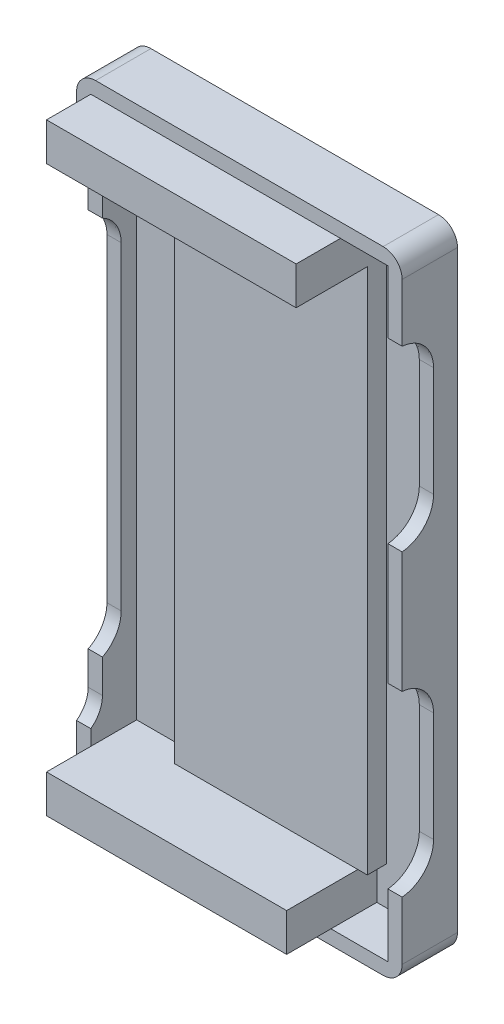
SolidWorks part; units mm, degrees
ref_plane "Front Plane" through (0, 0, 0) normal (0, 0, 1) x (1, 0, 0)
ref_plane "Top Plane" through (0, 0, 0) normal (0, 1, 0) x (1, 0, 0)
ref_plane "Right Plane" through (0, 0, 0) normal (1, 0, 0) x (0, 0, -1)
sketch "Sketch1" plane through (0, 0, 0) normal (0, 0, 1) x (1, 0, 0)
  line L0 (-32.3, 64.5) -> (2, 64.5)
  line L1 (-30.3, 62.5) -> (0, 62.5) construction
  line L2 (-30.3, 62.5) -> (-30.3, 0) construction
  line L3 (-30.3, 0) -> (0, 0) construction
  line L4 (0, 62.5) -> (0, 0) construction
  line L5 (2, 64.5) -> (2, -2)
  line L6 (-32.3, -2) -> (2, -2)
  line L7 (-32.3, 64.5) -> (-32.3, -2)
  dimension "D1" = 2
extrude "Boss-Extrude3" add sketch "Sketch1" along normal offset from surface 1.5 and the other way offset from surface (16.5814 mm away) 1.5
sketch "Sketch3" plane through (-32.3, 0, 0) normal (-1, 0, 0) x (0, 0, 1)
  line L0 (-13.4464, 47.86) -> (-13.4464, 14.26) construction
  line L1 (-9.7847, 11.1874) -> (-6.7947, 11.7146) construction
  line L2 (-4.2164, 14.7872) -> (-4.2164, 47.3328) construction
  line L3 (-6.7947, 50.4054) -> (-9.7847, 50.9326) construction
  line L5 (-13.9464, 47.86) -> (-13.9464, 14.26)
  line L6 (-9.6978, 10.695) -> (-6.7078, 11.2222)
  line L12 (-13.4464, 47.86) -> (-13.4464, 14.26) construction
  line L13 (-9.7847, 11.1874) -> (-6.7947, 11.7146) construction
  line L14 (-4.2164, 14.7872) -> (-4.2164, 47.3328) construction
  line L15 (-6.7947, 50.4054) -> (-9.7847, 50.9326) construction
  line L16 (-3.7164, 14.7872) -> (-3.7164, 47.3328)
  line L17 (-6.7078, 50.8978) -> (-9.6978, 51.425)
  spline S0 degree 3 poles (-13.4464, 14.26) (-13.4464, 12.1686) (-11.8443, 10.8242) (-9.7847, 11.1874) knots 0 0 0 0 1 1 1 1 weights 1 0.761858 0.761858 1 construction
  spline S1 degree 3 poles (-6.7947, 11.7146) (-5.2347, 11.9897) (-4.2164, 13.2032) (-4.2164, 14.7872) knots 0 0 0 0 1 1 1 1 weights 1 0.84403 0.84403 1 construction
  spline S2 degree 3 poles (-4.2164, 47.3328) (-4.2164, 48.9169) (-5.2347, 50.1303) (-6.7947, 50.4054) knots 0 0 0 0 1 1 1 1 weights 1 0.84403 0.84403 1 construction
  spline S3 degree 3 poles (-9.7847, 50.9326) (-11.8443, 51.2958) (-13.4464, 49.9514) (-13.4464, 47.86) knots 0 0 0 0 1 1 1 1 weights 1 0.761858 0.761858 1 construction
  spline S4 degree 3 poles (-13.4464, 14.26) (-13.4464, 12.1686) (-11.8443, 10.8242) (-9.7847, 11.1874) knots 0 0 0 0 1 1 1 1 weights 1 0.761858 0.761858 1 construction
  spline S5 degree 3 poles (-6.7947, 11.7146) (-5.2347, 11.9897) (-4.2164, 13.2032) (-4.2164, 14.7872) knots 0 0 0 0 1 1 1 1 weights 1 0.84403 0.84403 1 construction
  spline S6 degree 3 poles (-4.2164, 47.3328) (-4.2164, 48.9169) (-5.2347, 50.1303) (-6.7947, 50.4054) knots 0 0 0 0 1 1 1 1 weights 1 0.84403 0.84403 1 construction
  spline S7 degree 3 poles (-9.7847, 50.9326) (-11.8443, 51.2958) (-13.4464, 49.9514) (-13.4464, 47.86) knots 0 0 0 0 1 1 1 1 weights 1 0.761858 0.761858 1 construction
  spline S8 degree 1 poles (-13.9464, 14.26) (-9.6978, 10.695) knots 0 0 1 1 construction
  spline S9 degree 1 poles (-6.7078, 11.2222) (-3.7164, 14.7872) knots 0 0 1 1 construction
  spline S10 degree 1 poles (-3.7164, 47.3328) (-6.7078, 50.8978) knots 0 0 1 1 construction
  spline S11 degree 1 poles (-9.6978, 51.425) (-13.9464, 47.86) knots 0 0 1 1 construction
  spline S12 degree 3 poles (-13.9464, 14.26) (-13.9464, 14.0193) (-13.9017, 13.5499) (-13.5942, 12.5442) (-12.7412, 11.3822) (-11.4487, 10.7439) (-10.4049, 10.6158) (-9.9349, 10.6532) (-9.6978, 10.695) knots 0 0 0 0 0.125 0.25 0.5 0.75 0.875 1 1 1 1
  spline S13 degree 3 poles (-6.7078, 11.2222) (-6.308, 11.2927) (-5.5445, 11.5574) (-4.4978, 12.4053) (-3.8445, 13.5834) (-3.7164, 14.3812) (-3.7164, 14.7872) knots 0 0 0 0 0.25 0.5 0.75 1 1 1 1
  spline S14 degree 3 poles (-3.7164, 47.3328) (-3.7164, 47.7388) (-3.8445, 48.5366) (-4.4978, 49.7147) (-5.5445, 50.5626) (-6.308, 50.8273) (-6.7078, 50.8978) knots 0 0 0 0 0.25 0.5 0.75 1 1 1 1
  spline S15 degree 3 poles (-9.6978, 51.425) (-9.9349, 51.4668) (-10.4049, 51.5042) (-11.4487, 51.3761) (-12.7412, 50.7379) (-13.5942, 49.5758) (-13.9017, 48.5701) (-13.9464, 48.1007) (-13.9464, 47.86) knots 0 0 0 0 0.125 0.25 0.5 0.75 0.875 1 1 1 1
  dimension "D1" = 0.5
extrude "Cut-Extrude1" cut sketch "Sketch3" against normal blind 5
sketch "Sketch4" plane through (2, 0, 0) normal (1, 0, 0) x (0, 0, -1)
  line L0 (6.9047, 38.7046) -> (9.8947, 38.1774) construction
  line L1 (4.3264, 52.2728) -> (4.3264, 41.7772) construction
  line L2 (13.5564, 41.25) -> (13.5564, 52.8) construction
  line L3 (9.8947, 55.8726) -> (6.9047, 55.3454) construction
  line L4 (6.9047, 38.7046) -> (9.8947, 38.1774) construction
  line L5 (4.3264, 52.2728) -> (4.3264, 41.7772) construction
  line L6 (13.5564, 41.25) -> (13.5564, 52.8) construction
  line L7 (9.8947, 55.8726) -> (6.9047, 55.3454) construction
  line L8 (4.3264, 20.7728) -> (4.3264, 10.2772) construction
  line L9 (6.9047, 7.2046) -> (9.8947, 6.6774) construction
  line L10 (13.5564, 9.75) -> (13.5564, 21.3) construction
  line L11 (9.8947, 24.3726) -> (6.9047, 23.8454) construction
  line L12 (4.3264, 20.7728) -> (4.3264, 10.2772) construction
  line L13 (6.9047, 7.2046) -> (9.8947, 6.6774) construction
  line L14 (13.5564, 9.75) -> (13.5564, 21.3) construction
  line L15 (9.8947, 24.3726) -> (6.9047, 23.8454) construction
  line L16 (6.8178, 38.2122) -> (9.8078, 37.685)
  line L17 (14.0564, 41.25) -> (14.0564, 52.8)
  line L18 (9.8078, 56.365) -> (6.8178, 55.8378)
  line L19 (3.8264, 52.2728) -> (3.8264, 41.7772)
  line L20 (3.8264, 20.7728) -> (3.8264, 10.2772)
  line L21 (6.8178, 6.7122) -> (9.8078, 6.185)
  line L22 (14.0564, 9.75) -> (14.0564, 21.3)
  line L23 (9.8078, 24.865) -> (6.8178, 24.3378)
  spline S0 degree 3 poles (4.3264, 41.7772) (4.3264, 40.1932) (5.3447, 38.9797) (6.9047, 38.7046) knots 0 0 0 0 1 1 1 1 weights 1 0.84403 0.84403 1 construction
  spline S1 degree 3 poles (9.8947, 38.1774) (11.9543, 37.8142) (13.5564, 39.1586) (13.5564, 41.25) knots 0 0 0 0 1 1 1 1 weights 1 0.761858 0.761858 1 construction
  spline S2 degree 3 poles (6.9047, 55.3454) (5.3447, 55.0703) (4.3264, 53.8568) (4.3264, 52.2728) knots 0 0 0 0 1 1 1 1 weights 1 0.84403 0.84403 1 construction
  spline S3 degree 3 poles (13.5564, 52.8) (13.5564, 54.8914) (11.9543, 56.2358) (9.8947, 55.8726) knots 0 0 0 0 1 1 1 1 weights 1 0.761858 0.761858 1 construction
  spline S4 degree 3 poles (4.3264, 41.7772) (4.3264, 40.1932) (5.3447, 38.9797) (6.9047, 38.7046) knots 0 0 0 0 1 1 1 1 weights 1 0.84403 0.84403 1 construction
  spline S5 degree 3 poles (9.8947, 38.1774) (11.9543, 37.8142) (13.5564, 39.1586) (13.5564, 41.25) knots 0 0 0 0 1 1 1 1 weights 1 0.761858 0.761858 1 construction
  spline S6 degree 3 poles (6.9047, 55.3454) (5.3447, 55.0703) (4.3264, 53.8568) (4.3264, 52.2728) knots 0 0 0 0 1 1 1 1 weights 1 0.84403 0.84403 1 construction
  spline S7 degree 3 poles (13.5564, 52.8) (13.5564, 54.8914) (11.9543, 56.2358) (9.8947, 55.8726) knots 0 0 0 0 1 1 1 1 weights 1 0.761858 0.761858 1 construction
  spline S8 degree 3 poles (4.3264, 10.2772) (4.3264, 8.6932) (5.3447, 7.4797) (6.9047, 7.2046) knots 0 0 0 0 1 1 1 1 weights 1 0.84403 0.84403 1 construction
  spline S9 degree 3 poles (9.8947, 6.6774) (11.9543, 6.3142) (13.5564, 7.6586) (13.5564, 9.75) knots 0 0 0 0 1 1 1 1 weights 1 0.761858 0.761858 1 construction
  spline S10 degree 3 poles (6.9047, 23.8454) (5.3447, 23.5703) (4.3264, 22.3568) (4.3264, 20.7728) knots 0 0 0 0 1 1 1 1 weights 1 0.84403 0.84403 1 construction
  spline S11 degree 3 poles (13.5564, 21.3) (13.5564, 23.3914) (11.9543, 24.7358) (9.8947, 24.3726) knots 0 0 0 0 1 1 1 1 weights 1 0.761858 0.761858 1 construction
  spline S12 degree 3 poles (4.3264, 10.2772) (4.3264, 8.6932) (5.3447, 7.4797) (6.9047, 7.2046) knots 0 0 0 0 1 1 1 1 weights 1 0.84403 0.84403 1 construction
  spline S13 degree 3 poles (9.8947, 6.6774) (11.9543, 6.3142) (13.5564, 7.6586) (13.5564, 9.75) knots 0 0 0 0 1 1 1 1 weights 1 0.761858 0.761858 1 construction
  spline S14 degree 3 poles (6.9047, 23.8454) (5.3447, 23.5703) (4.3264, 22.3568) (4.3264, 20.7728) knots 0 0 0 0 1 1 1 1 weights 1 0.84403 0.84403 1 construction
  spline S15 degree 3 poles (13.5564, 21.3) (13.5564, 23.3914) (11.9543, 24.7358) (9.8947, 24.3726) knots 0 0 0 0 1 1 1 1 weights 1 0.761858 0.761858 1 construction
  spline S16 degree 1 poles (9.8078, 37.685) (14.0564, 41.25) knots 0 0 1 1 construction
  spline S17 degree 1 poles (14.0564, 52.8) (9.8078, 56.365) knots 0 0 1 1 construction
  spline S18 degree 1 poles (6.8178, 55.8378) (3.8264, 52.2728) knots 0 0 1 1 construction
  spline S19 degree 1 poles (3.8264, 41.7772) (6.8178, 38.2122) knots 0 0 1 1 construction
  spline S20 degree 3 poles (9.8078, 37.685) (10.0449, 37.6432) (10.5149, 37.6058) (11.5587, 37.7339) (12.8512, 38.3721) (13.7042, 39.5342) (14.0117, 40.5399) (14.0564, 41.0093) (14.0564, 41.25) knots 0 0 0 0 0.125 0.25 0.5 0.75 0.875 1 1 1 1
  spline S21 degree 3 poles (14.0564, 52.8) (14.0564, 53.0407) (14.0117, 53.5101) (13.7042, 54.5158) (12.8512, 55.6778) (11.5587, 56.3161) (10.5149, 56.4442) (10.0449, 56.4068) (9.8078, 56.365) knots 0 0 0 0 0.125 0.25 0.5 0.75 0.875 1 1 1 1
  spline S22 degree 3 poles (6.8178, 55.8378) (6.418, 55.7673) (5.6545, 55.5026) (4.6078, 54.6547) (3.9545, 53.4766) (3.8264, 52.6788) (3.8264, 52.2728) knots 0 0 0 0 0.25 0.5 0.75 1 1 1 1
  spline S23 degree 3 poles (3.8264, 41.7772) (3.8264, 41.3712) (3.9545, 40.5734) (4.6078, 39.3953) (5.6545, 38.5474) (6.418, 38.2827) (6.8178, 38.2122) knots 0 0 0 0 0.25 0.5 0.75 1 1 1 1
  spline S24 degree 1 poles (3.8264, 10.2772) (6.8178, 6.7122) knots 0 0 1 1 construction
  spline S25 degree 1 poles (9.8078, 6.185) (14.0564, 9.75) knots 0 0 1 1 construction
  spline S26 degree 1 poles (14.0564, 21.3) (9.8078, 24.865) knots 0 0 1 1 construction
  spline S27 degree 1 poles (6.8178, 24.3378) (3.8264, 20.7728) knots 0 0 1 1 construction
  spline S28 degree 3 poles (3.8264, 10.2772) (3.8264, 9.8712) (3.9545, 9.0734) (4.6078, 7.8953) (5.6545, 7.0474) (6.418, 6.7827) (6.8178, 6.7122) knots 0 0 0 0 0.25 0.5 0.75 1 1 1 1
  spline S29 degree 3 poles (9.8078, 6.185) (10.0449, 6.1432) (10.5149, 6.1058) (11.5587, 6.2339) (12.8512, 6.8722) (13.7042, 8.0342) (14.0117, 9.0399) (14.0564, 9.5093) (14.0564, 9.75) knots 0 0 0 0 0.125 0.25 0.5 0.75 0.875 1 1 1 1
  spline S30 degree 3 poles (14.0564, 21.3) (14.0564, 21.5407) (14.0117, 22.0101) (13.7042, 23.0158) (12.8512, 24.1779) (11.5587, 24.8161) (10.5149, 24.9442) (10.0449, 24.9068) (9.8078, 24.865) knots 0 0 0 0 0.125 0.25 0.5 0.75 0.875 1 1 1 1
  spline S31 degree 3 poles (6.8178, 24.3378) (6.418, 24.2673) (5.6545, 24.0026) (4.6078, 23.1547) (3.9545, 21.9766) (3.8264, 21.1788) (3.8264, 20.7728) knots 0 0 0 0 0.25 0.5 0.75 1 1 1 1
  dimension "D1" = 0.5
extrude "Cut-Extrude2" cut sketch "Sketch4" against normal blind 5
fillet "Fillet1" radius 2 4 edges at (2, -2, -6.6657) (-32.3, -2, -6.6657) (-32.3, 64.5, -6.6657) (2, 64.5, -6.6657)
sketch "Sketch5" plane through (0, 0, 3.25) normal (0, 0, 1) x (1, 0, 0)
  line L1 (-38.4696, 67.7647) -> (12.8382, 67.7647)
  line L2 (-38.4696, 67.7647) -> (-38.4696, -8.6352)
  line L3 (-38.4696, -8.6352) -> (12.8382, -8.6352)
  line L4 (12.8382, 67.7647) -> (12.8382, -8.6352)
extrude "Cut-Extrude3" cut sketch "Sketch5" against normal blind 14
sketch "Sketch6" plane through (0, 0, -10.75) normal (0, 0, 1) x (1, 0, 0)
  line L0 (0, 64.5) -> (-30.3, 64.5) construction
  line L1 (-30.8, 63) -> (0.5, 63)
  line L2 (-30.8, 63) -> (-30.8, -0.5)
  line L3 (-30.8, -0.5) -> (0.5, -0.5)
  line L4 (0.5, 63) -> (0.5, -0.5)
  line L5 (-32.3, 62.5) -> (-32.3, 51.4549) construction
  line L6 (2, 56.4062) -> (2, 62.5) construction
  line L7 (-30.3, -2) -> (0, -2) construction
  dimension "D1" = 1.5
  dimension "D2" = 1.5
  dimension "D3" = 1.5
  dimension "D4" = 1.5
extrude "Cut-Extrude4" cut sketch "Sketch6" against normal offset from surface (4.8314 mm away) 1 up to face at (-15.15, 31.25, -16.5814)
sketch "Sketch7" plane through (0, 0, -15.5814) normal (0, 0, 1) x (1, 0, 0)
  line L0 (0.5, 63) -> (-30.8, 63) construction
  line L1 (-30.8, 63) -> (-4.5, 63)
  line L2 (-30.8, 63) -> (-30.8, 59)
  line L3 (-30.8, 59) -> (-4.5, 59)
  line L4 (-4.5, 63) -> (-4.5, 59)
  line L5 (-30.8, -0.5) -> (0.5, -0.5) construction
  line L6 (-30.8, -0.5) -> (-5.5, -0.5)
  line L7 (-30.8, -0.5) -> (-30.8, 3.5)
  line L8 (-30.8, 3.5) -> (-5.5, 3.5)
  line L9 (-5.5, -0.5) -> (-5.5, 3.5)
  line L10 (0.5, -0.5) -> (0.5, 63) construction
  line L11 (-30.8, 63) -> (-30.8, -0.5) construction
  dimension "D1" = 4
  dimension "D2" = 6
  dimension "D3" = 0
  dimension "D4" = 4
  dimension "D5" = 5
  dimension "D6" = 0
extrude "Boss-Extrude4" add sketch "Sketch7" along normal blind 9.5
sketch "Sketch8" plane through (0, 0, -15.5814) normal (0, 0, 1) x (1, 0, 0)
  line L0 (-5.5, 3.5) -> (-30.8, 3.5) construction
  line L1 (-4.5, 59) -> (-24.8, 59)
  line L2 (-4.5, 59) -> (-4.5, 3.5)
  line L3 (-4.5, 3.5) -> (-24.8, 3.5)
  line L4 (-24.8, 59) -> (-24.8, 3.5)
  line L5 (-30.8, 59) -> (-30.8, 3.5) construction
  dimension "D1" = 6
extrude "Boss-Extrude5" add sketch "Sketch8" along normal blind 2
sketch "Sketch9" plane through (-32.3, 0, 0) normal (-1, 0, 0) x (0, 0, 1)
  line L2 (-11.9741, 54.6351) -> (-11.9741, 7.533)
  line L4 (-5.9741, 54.6351) -> (-5.9741, 7.533)
  arc A0 (-11.9741, 7.533) -> (-5.9741, 7.533) centre (-8.9741, 7.533) ccw
  arc A1 (-5.9741, 54.6351) -> (-11.9741, 54.6351) centre (-8.9741, 54.6351) ccw
extrude "Cut-Extrude5" cut sketch "Sketch9" against normal up to surface (1.5 mm away) up to face at (-30.8, 30.7056, -12.757)
